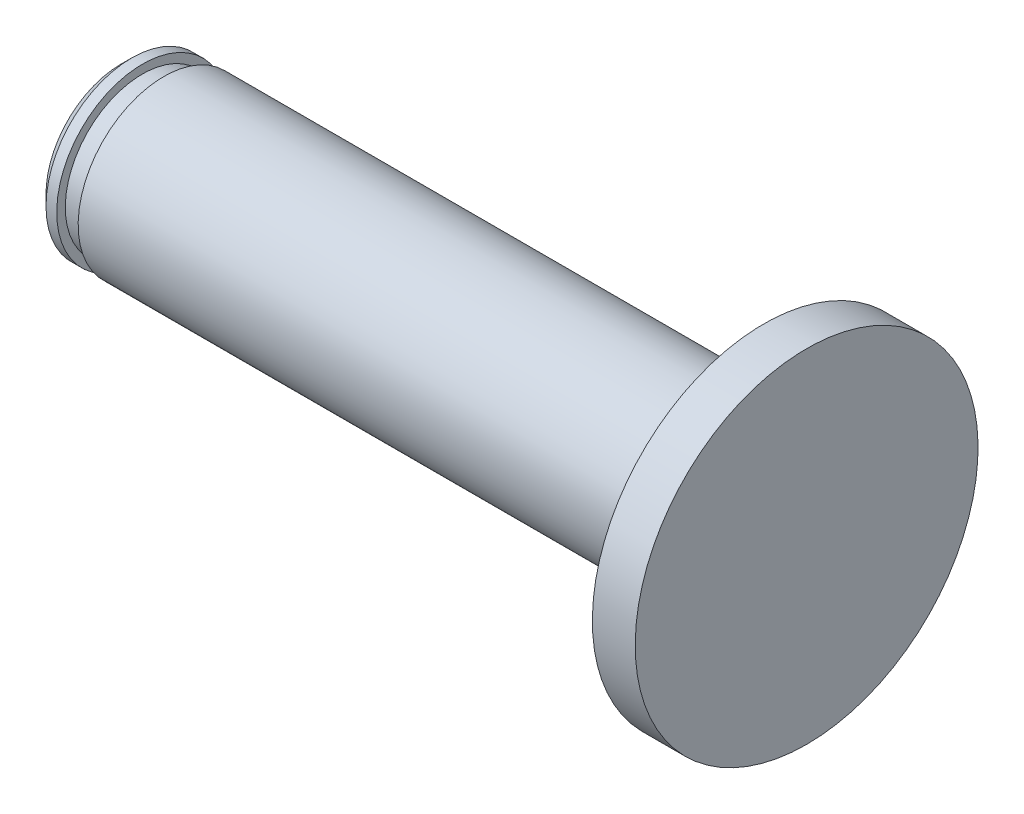
SolidWorks part; units mm, degrees
ref_plane "Спереди" through (0, 0, 0) normal (0, 0, 1) x (1, 0, 0)
ref_plane "Сверху" through (0, 0, 0) normal (0, 1, 0) x (1, 0, 0)
ref_plane "Справа" through (0, 0, 0) normal (1, 0, 0) x (0, 0, -1)
sketch "Эскиз1" plane through (0, 0, 0) normal (0, 0, 1) x (1, 0, 0)
  line L0 (0, 0) -> (-32, 0)
  line L1 (-32, 0) -> (-32, 4)
  line L2 (-32, 4) -> (-31, 4)
  line L3 (-31, 4) -> (-31, 3.6)
  line L4 (-31, 3.6) -> (-30, 3.6)
  line L5 (-30, 3.6) -> (-30, 4)
  line L6 (-30, 4) -> (-2, 4)
  line L7 (-2, 4) -> (-2, 8)
  line L8 (-2, 8) -> (0, 8)
  line L9 (0, 8) -> (0, 0)
  line L10 (-32, 0) -> (-24.8571, 0) construction
  line L11 (-32, 0) -> (-50032, 0) construction
  dimension "D1" = 8
  dimension "D2" = 28
  dimension "D3" = 2
  dimension "D4" = 4
  dimension "D5" = 1
  dimension "D6" = 1
  dimension "D7" = 7.2
revolve "Повернуть1" add sketch "Эскиз1" angle 360 about L10
chamfer "Фаска1" distance 0.5 angle 45 1 edges at (-32, -4, 0)
equation "\"Диаметр вала\" = 8  '!!!"
equation "\"Длина вала\" = 28"
equation "\"D1@Эскиз1\"=\"Диаметр вала\""
equation "\"D2@Эскиз1\"=\"Длина вала\""
